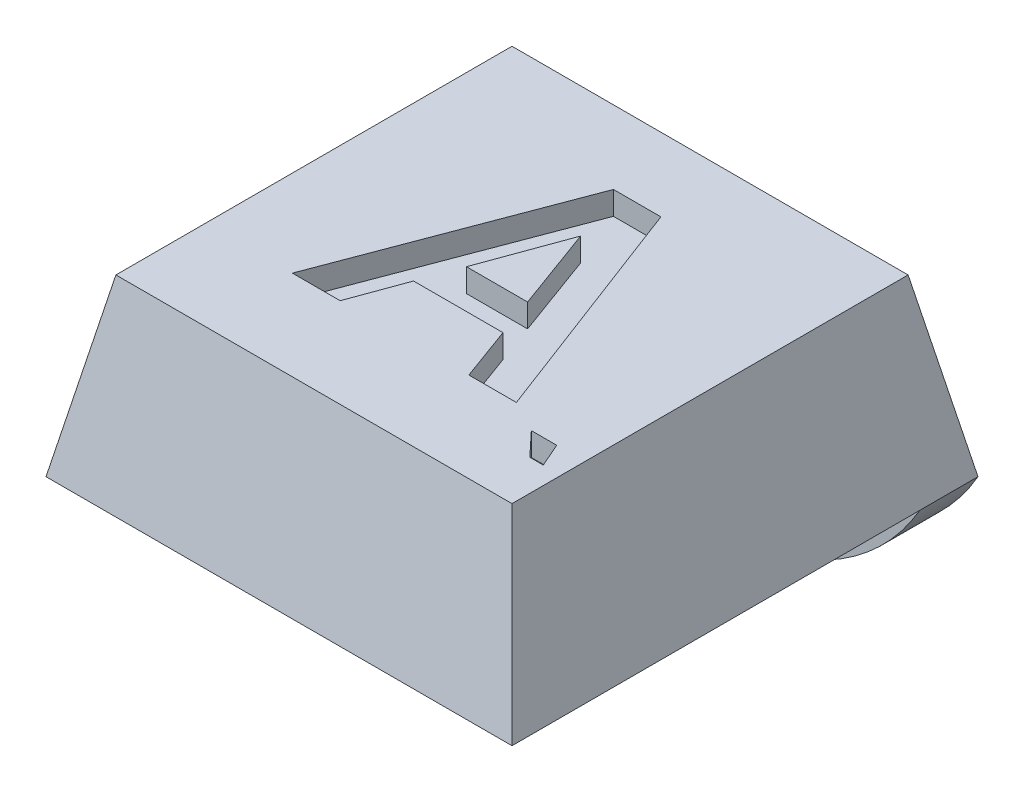
SolidWorks part; units mm, degrees
ref_plane "Front Plane" through (0, 0, 0) normal (0, 0, 1) x (1, 0, 0)
ref_plane "Top Plane" through (0, 0, 0) normal (0, 1, 0) x (1, 0, 0)
ref_plane "Right Plane" through (0, 0, 0) normal (1, 0, 0) x (0, 0, -1)
sketch "Sketch1" plane through (0, 0, 0) normal (0, 1, 0) x (1, 0, 0)
  line L1 (0, 0) -> (8, 0)
  line L2 (0, 0) -> (0, 8)
  line L3 (0, 8) -> (8, 8)
  line L4 (8, 0) -> (8, 8)
  dimension "D1" = 8
  dimension "D2" = 8
extrude "Boss-Extrude1" add sketch "Sketch1" along normal blind 3
sketch "Sketch2" plane through (0, 0, 0) normal (0, 0, 1) x (1, 0, 0)
  line L0 (0, 0) -> (0.6, 3)
  line L1 (0, 3) -> (8, 3) construction
  line L2 (0.6, 3) -> (0, 3)
  line L3 (0, 3) -> (0, 0)
  line L4 (8, 0) -> (7.4, 3)
  line L5 (7.4, 3) -> (8, 3)
  line L6 (8, 3) -> (8, 0)
  dimension "D1" = 0.6
  dimension "D2" = 0.6
extrude "Cut-Extrude1" cut sketch "Sketch2" against normal through all both and the other way through all
sketch "Sketch3" plane through (0, 0, 0) normal (1, 0, 0) x (0, 0, -1)
  line L0 (0, 0) -> (0.6, 3)
  line L1 (8, 3) -> (0, 3) construction
  line L2 (0.6, 3) -> (0, 3)
  line L3 (0, 3) -> (0, 0)
  line L4 (8, 3) -> (7.4, 3)
  line L5 (7.4, 3) -> (8, 0)
  line L6 (8, 3) -> (8, 0)
  dimension "D1" = 0.6
  dimension "D2" = 0.6
extrude "Cut-Extrude2" cut sketch "Sketch3" along normal blind 11
sketch "Sketch4" plane through (0, 0, 0) normal (0, -1, 0) x (1, 0, 0)
  line L0 (8, 0) -> (8, -8) construction
  line L3 (0, 0) -> (8, 0) construction
  circle A0 centre (4, -3.75) radius 1.8
  dimension "D1" = 3.6
  dimension "D2" = 4
  dimension "D3" = 3.75
extrude "Cut-Extrude3" cut sketch "Sketch4" against normal blind 0.8
sketch "Sketch5" plane through (0, 0, 0) normal (0, -1, 0) x (1, 0, 0)
  line L0 (8, 0) -> (8, -8) construction
  line L1 (0, -8) -> (8, -8)
  line L2 (0, -8) -> (0, -7)
  line L3 (0, -7) -> (8, -7)
  line L4 (8, -8) -> (8, -7)
  dimension "D1" = 1
extrude "Boss-Extrude2" add sketch "Sketch5" along normal blind 2
fillet "Fillet1" radius 4 2 edges at (8, -2, -7.5) (0, -2, -7.5)
sketch "Sketch6" plane through (0, 3, 0) normal (0, 1, 0) x (1, 0, 0)
  text T0 "A" font "Arial" height 4
extrude "Cut-Extrude4" cut sketch "Sketch6" against normal blind 0.4
sketch "Sketch7" plane through (0, 3, 0) normal (0, 1, 0) x (1, 0, 0)
  text T0 "`" font "Arial" height 2
extrude "Cut-Extrude5" cut sketch "Sketch7" against normal blind 0.4
